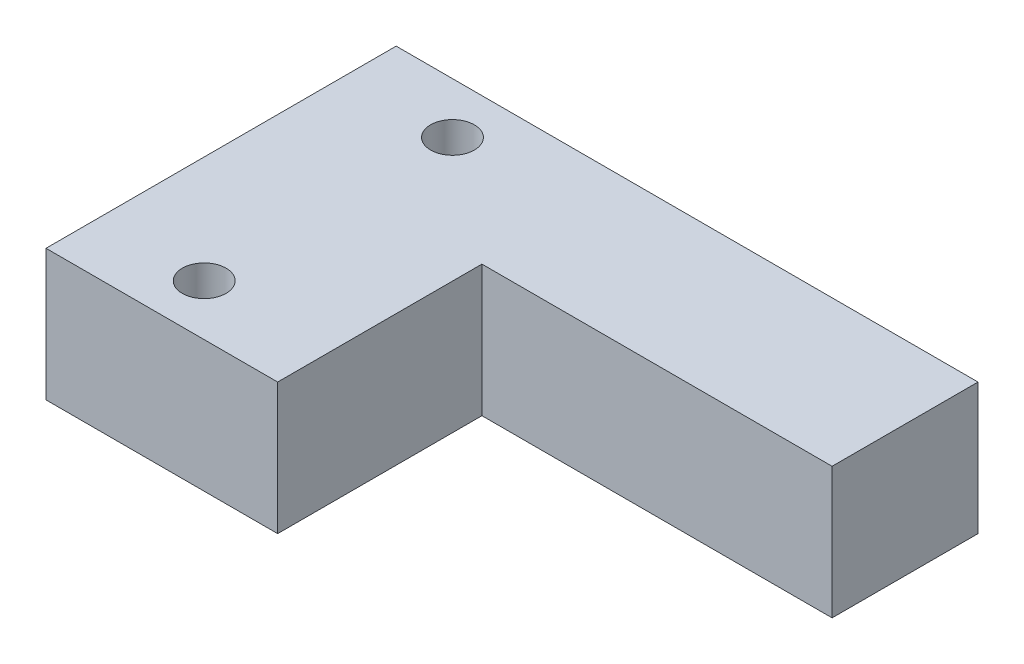
SolidWorks part; units mm, degrees
ref_plane "Front Plane" through (0, 0, 0) normal (0, 0, 1) x (1, 0, 0)
ref_plane "Top Plane" through (0, 0, 0) normal (0, 1, 0) x (1, 0, 0)
ref_plane "Right Plane" through (0, 0, 0) normal (1, 0, 0) x (0, 0, -1)
sketch "Sketch1" plane through (0, 0, 0) normal (0, 1, 0) x (1, 0, 0)
  line L1 (-19.939, -12) -> (19.939, -12)
  line L2 (-19.939, -12) -> (-19.939, 12)
  line L3 (-19.939, 12) -> (19.939, 12)
  line L4 (19.939, -12) -> (19.939, 12)
  circle A0 centre (-14.5292, -8.1486) radius 1.5
  circle A1 centre (-14.5292, 8.8694) radius 1.5
  point P4 (-19.939, 0)
  point P6 (0, -12)
  point P11 (-14.5292, -8.1486)
  dimension "D4" = 3
  dimension "D1" = 39.878
  dimension "D2" = 24
  dimension "D3" = 17.018
extrude "Boss-Extrude1" add sketch "Sketch1" along normal blind 9 contours L3 L4 L1 L2
sketch "Sketch2" plane through (0, 9, 0) normal (0, 1, 0) x (1, 0, 0)
  line L0 (-19.939, -12) -> (19.939, -12) construction
  line L1 (-4.061, -12) -> (19.939, -12)
  line L2 (-4.061, -12) -> (-4.061, 2)
  line L3 (-4.061, 2) -> (19.939, 2)
  line L4 (19.939, -12) -> (19.939, 2)
  line L5 (19.939, -12) -> (19.939, 12) construction
  dimension "D1" = 24
  dimension "D2" = 14
extrude "Cut-Extrude1" cut sketch "Sketch2" against normal through all
sketch "Sketch4" plane through (0, 9, 0) normal (0, 1, 0) x (1, 0, 0)
  line L0 (-19.939, -12) -> (-19.939, 12) construction
  line L1 (-12.589, 8.509) -> (-12.589, -8.509) construction
  circle A0 centre (-12.589, -8.509) radius 1.5
  circle A1 centre (-12.589, 8.509) radius 1.5
  point P6 (-12.589, 9.3095)
  point P7 (-12.589, 5.9105)
  point P8 (-19.939, 0)
  point P9 (-12.589, 0)
  dimension "D2" = 3
  dimension "D1" = 17.018
  dimension "D3" = 7.35
extrude "Cut-Extrude2" cut sketch "Sketch4" against normal through all
